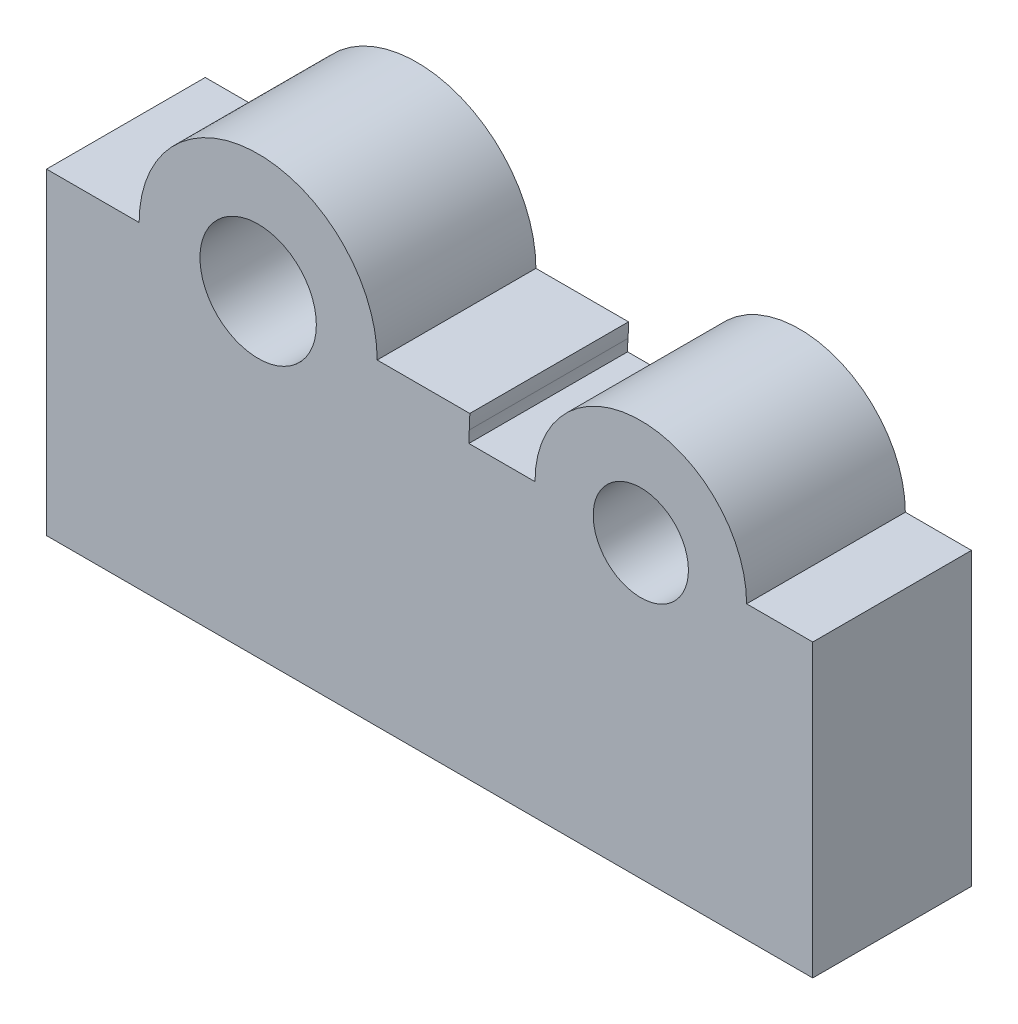
SolidWorks part; units mm, degrees
ref_plane "Front Plane" through (0, 0, 0) normal (0, 0, 1) x (1, 0, 0)
ref_plane "Top Plane" through (0, 0, 0) normal (0, 1, 0) x (1, 0, 0)
ref_plane "Right Plane" through (0, 0, 0) normal (1, 0, 0) x (0, 0, -1)
sketch "Sketch1" plane through (0, 0, 0) normal (0, 0, 1) x (1, 0, 0)
  line L7 (-112.3274, 5) -> (-32.3274, 5)
  line L8 (-112.3274, 5) -> (-112.3274, -55)
  line L9 (-112.3274, -55) -> (-32.3274, -55)
  line L11 (32.5, 0) -> (-32.5, 0)
  line L12 (32.5, 0) -> (32.5, -55)
  line L13 (32.5, -55) -> (-32.5, -55)
  line L14 (-32.5, 0) -> (-32.5, -55)
  circle A0 centre (0, 0) radius 32.5
  circle A1 centre (0, 0) radius 4.1
  circle A2 centre (-72.3274, 5) radius 10
  circle A3 centre (-72.3274, 5) radius 40
  circle A4 centre (0, 0) radius 11.2
  point P9 (72.7387, 16.0127)
  point P17 (-72.0519, 8.0483)
  point P18 (0, 0)
  point P24 (-72.3274, 5)
  dimension "D1" = 8.2
  dimension "D2" = 65
  dimension "D3" = 20
  dimension "D4" = 80
  dimension "D5" = 60
  dimension "D6" = 22.4
  dimension "D7" = 5
extrude "Boss-Extrude2" add sketch "Sketch1" along normal blind 30 contours A3 L8 L9 | L7 A3 A2 | A0 L13 L12 | A4 L11 A0 region at (-72.3274, -12.8254, 0) region at (-72.5011, -39.3704, 0) region at (0, -15.0117, 0) region at (0, -39.3701, 0)
sketch "Sketch2" plane through (0, 0, 30) normal (0, 0, 1) x (1, 0, 0)
  line L0 (-72.3274, -5) -> (-72.3274, -55) construction
  line L1 (-112.3274, -55) -> (32.5, -55) construction
  arc A0 (-82.3274, 5) -> (-62.3274, 5) centre (-72.3274, 5) ccw construction
sketch "Sketch3" plane through (0, 0, 0) normal (0, 0, 1) x (1, 0, 0)
  circle A0 centre (0, 0) radius 11.2
  circle A1 centre (0, 0) radius 20
  circle A2 centre (0, 0) radius 9
  dimension "D1" = 22.4
  dimension "D2" = 40
  dimension "D3" = 18
extrude "Boss-Extrude3" add sketch "Sketch3" against normal up to surface (30 mm away) from surface contours A1 | A0 up to face at (-36.505, -9.9053, 0) starting at face at (-36.505, -9.9053, 30)
extrude "Boss-Extrude5" add sketch "Sketch3<7>" against normal blind 23 from surface contours A0 A2 region at (-10.8832, 0, 0) starting at face at (11.2, 0, 30)
sketch "Sketch3<7>" plane through (0, 0, 0) normal (0, 0, 1) x (1, 0, 0) same geometry as "Sketch3"
sketch "Sketch4" plane through (0, 0, 0) normal (0, 0, 1) x (1, 0, 0)
  circle A1 centre (-72.3274, 5) radius 13.2
  circle A2 centre (-72.3274, 5) radius 22.5
  circle A3 centre (-72.3274, 5) radius 11
  dimension "D1" = 45
  dimension "D2" = 26.4
  dimension "D3" = 22
extrude "Boss-Extrude6" add sketch "Sketch4" against normal up to surface (30 mm away) from surface contours A2 up to face at (11.2, 0, 0) starting at face at (-36.505, -7.069, 30)
extrude "Cut-Extrude3" cut sketch "Sketch4<3>" along normal blind 10.2 from surface contours A1 starting at face at (-36.505, -4.1144, 0)
sketch "Sketch4<3>" plane through (0, 0, 0) normal (0, 0, 1) x (1, 0, 0) same geometry as "Sketch4"
extrude "Cut-Extrude5" cut sketch "Sketch4<5>" along normal through all contours A3
sketch "Sketch4<5>" plane through (0, 0, 0) normal (0, 0, 1) x (1, 0, 0) same geometry as "Sketch4"
